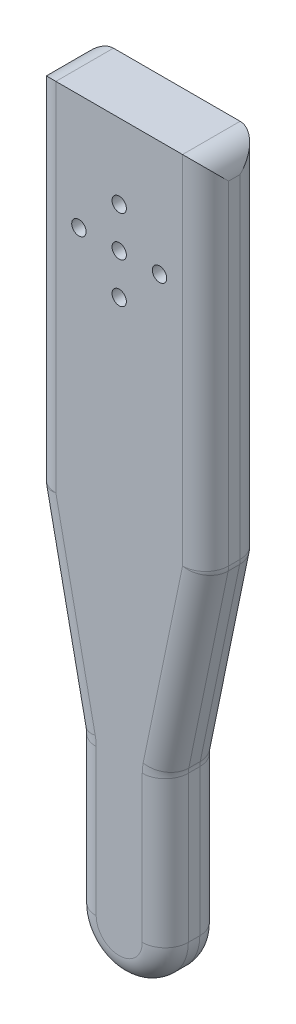
SolidWorks part; units mm, degrees
ref_plane "Front Plane" through (0, 0, 0) normal (0, 0, 1) x (1, 0, 0)
ref_plane "Top Plane" through (0, 0, 0) normal (0, 1, 0) x (1, 0, 0)
ref_plane "Right Plane" through (0, 0, 0) normal (1, 0, 0) x (0, 0, -1)
sketch "Sketch2" plane through (0, 0, 0) normal (0, 0, 1) x (1, 0, 0)
  line L1 (-29.8024, 62.3024) -> (0.1976, 62.3024)
  line L2 (-29.8024, 62.3024) -> (-29.8024, -67.6976)
  line L3 (-29.8024, -67.6976) -> (0.1976, -67.6976)
  line L4 (0.1976, 62.3024) -> (0.1976, -67.6976)
  dimension "D1" = 130
extrude "Boss-Extrude1" add sketch "Sketch2" along normal blind 10
sketch "Sketch3" plane through (0, 0, 10) normal (0, 0, 1) x (1, 0, 0)
  line L0 (-14.8024, 62.3024) -> (-14.8024, 42.3024)
  line L1 (0.1976, 62.3024) -> (-29.8024, 62.3024) construction
  line L4 (-29.8024, -67.6976) -> (-21.8024, -67.6976)
  line L5 (-29.8024, -67.6976) -> (-29.8024, 0)
  line L6 (-29.8024, 0) -> (-21.8024, 0)
  line L7 (-21.8024, -67.6976) -> (-21.8024, 0)
  line L9 (0, 0) -> (-7.8024, 0)
  line L10 (0, 0) -> (0, -67.6976)
  line L11 (0, -67.6976) -> (-7.8024, -67.6976)
  line L12 (-7.8024, 0) -> (-7.8024, -67.6976)
  line L13 (-29.8024, -67.6976) -> (0.1976, -67.6976) construction
  circle A0 centre (-14.8024, 42.3024) radius 7 construction
  circle A1 centre (-21.8024, 42.3024) radius 1.5
  circle A2 centre (-14.8024, 49.3024) radius 1.5
  circle A3 centre (-7.8024, 42.3024) radius 1.5
  circle A4 centre (-14.8024, 35.3024) radius 1.5
  point P5 (-21.8024, 42.3024)
  point P7 (-14.8024, 49.3024)
  point P9 (-7.8024, 42.3024)
  point P11 (-14.8024, 35.3024)
  point P463 (0, 0)
hole_wizard "M3x0.5 Tapped Hole2" positions "Sketch3" profile "Sketch5" tap size "M3x0.5" standard "ANSI Metric" end condition through all
sketch "Sketch5" plane through (-14.8024, 35.3024, 10) normal (1, 0, 0) x (0, -1, 0)
  line L0 (0, 0) -> (0, 10)
  line L1 (0, 10) -> (1.25, 10)
  line L2 (1.25, 10) -> (1.25, 0)
  line L5 (1.25, 0) -> (0, 0)
  line L11 (0, -6.35) -> (0, 107.95) construction
  dimension "Thru Tap Drill Dia." = 2.5
  dimension "Thru Tap Drill Depth" = 10
cosmetic thread "Hole Thread5" parameters "D2"=3
cosmetic thread "Hole Thread6" parameters "D2"=3
cosmetic thread "Hole Thread7" parameters "D2"=3
cosmetic thread "Hole Thread8" parameters "D2"=3
sketch "Sketch6" plane through (0, 0, 10) normal (0, 0, 1) x (1, 0, 0)
  line L1 (-29.8024, -67.6976) -> (-22.8024, -67.6976)
  line L2 (-29.8024, -67.6976) -> (-29.8024, 0)
  line L4 (-22.8024, -67.6976) -> (-22.8024, -33.8488)
  line L11 (0.1976, -67.6976) -> (-6.8024, -67.6976)
  line L12 (0.1976, -67.6976) -> (0.1976, 0)
  line L14 (-6.8024, -67.6976) -> (-6.8024, -33.8488)
  line L15 (-29.8024, 0) -> (-22.8024, -33.8488)
  line L16 (-6.8024, -33.8488) -> (0.1976, 0)
  dimension "D1" = 7
extrude "Cut-Extrude3" cut sketch "Sketch6" against normal through all contours L14 L16 L12 L11 | L4 L15 L2 L1
fillet "Fillet3" 2 edges at (-22.8024, -67.6976, 5) (-6.8024, -67.6976, 5) type full round first side face at (-22.8024, -50.7732, 5) second side face at (-6.8024, -50.7732, 5) middle face at (-14.8024, -67.6976, 5)
fillet "Fillet4" radius 4 20 edges at (-14.8024, -67.6976, 0) (-14.8024, -67.6976, 10) (-6.8024, -46.7732, 0) (-6.8024, -46.7732, 10) (-22.8024, -46.7732, 0) (-22.8024, -46.7732, 10) (0.1976, 31.1512, 10) (0.1976, 62.3024, 5) (0.1976, 31.1512, 0) (0.1976, 0, 5) (-3.3024, -16.9244, 0) (-6.8024, -33.8488, 5) (-3.3024, -16.9244, 10) (-22.8024, -33.8488, 5) (-26.3024, -16.9244, 0) (-26.3024, -16.9244, 10) (-29.8024, 31.1512, 0) (-29.8024, 62.3024, 5) (-29.8024, 31.1512, 10) (-29.8024, 0, 5)
sketch "Sketch8" plane through (0, 0, 10) normal (0, 0, 1) x (1, 0, 0)
  line L0 (-14.8024, 62.3024) -> (-14.8024, 34.0524)
  line L1 (-3.8024, 62.3024) -> (-25.8024, 62.3024) construction
  line L2 (-23.0524, 42.3024) -> (-6.5524, 42.3024)
  circle A0 centre (-14.8024, 35.3024) radius 1.25 construction
  circle A1 centre (-21.8024, 42.3024) radius 1.25 construction
  circle A2 centre (-7.8024, 42.3024) radius 1.25 construction
  point P13 (-14.8024, 42.3024)
hole_wizard "M3x0.5 Tapped Hole3" positions "Sketch8" profile "Sketch9" tap size "M3x0.5" standard "ANSI Metric" end condition through all
sketch "Sketch9" plane through (-14.8024, 42.3024, 10) normal (1, 0, 0) x (0, -1, 0)
  line L0 (0, 0) -> (0, 10)
  line L1 (0, 10) -> (1.25, 10)
  line L2 (1.25, 10) -> (1.25, 0)
  line L5 (1.25, 0) -> (0, 0)
  line L11 (0, -6.35) -> (0, 107.95) construction
  dimension "Thru Tap Drill Dia." = 2.5
  dimension "Thru Tap Drill Depth" = 10
cosmetic thread "Hole Thread9" parameters "D2"=3
